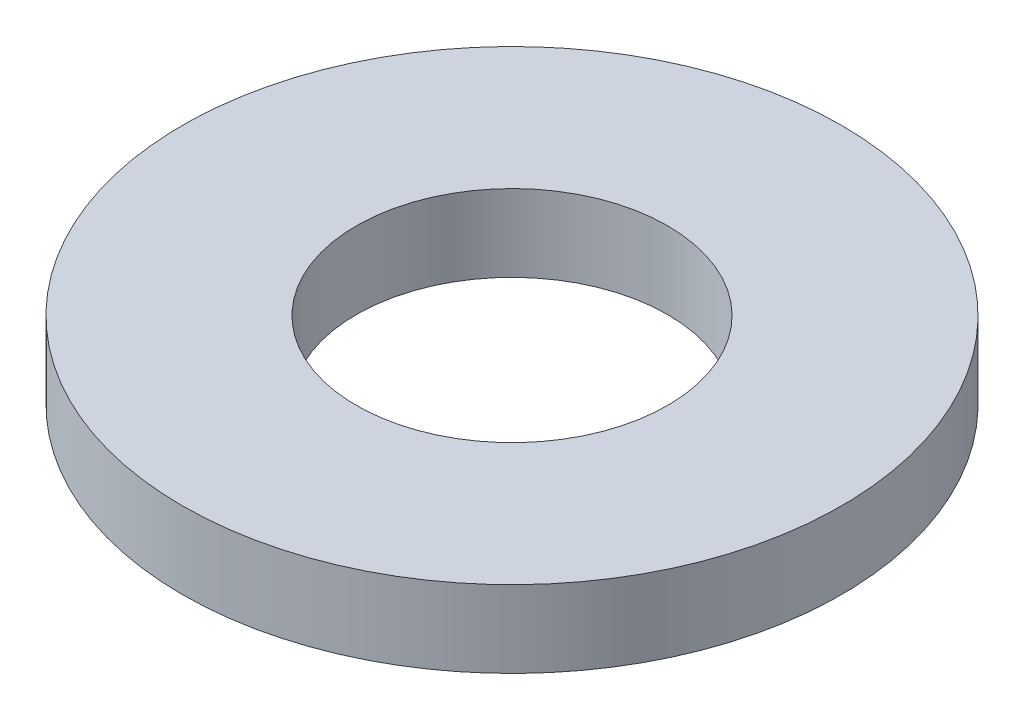
SolidWorks part; units mm, degrees
ref_plane "Front Plane" through (0, 0, 0) normal (0, 0, 1) x (1, 0, 0)
ref_plane "Top Plane" through (0, 0, 0) normal (0, 1, 0) x (1, 0, 0)
ref_plane "Right Plane" through (0, 0, 0) normal (1, 0, 0) x (0, 0, -1)
sketch "Sketch1" plane through (0, 0, 0) normal (0, 1, 0) x (1, 0, 0)
  circle A0 centre (0, 0) radius 90
  dimension "FLANGE_OD" = 180
extrude "Boss-Extrude1" add sketch "Sketch1" along normal blind 21
sketch "Sketch2" plane through (0, 0, 0) normal (0, 1, 0) x (1, 0, 0)
  circle A0 centre (0, 0) radius 42.5
  dimension "BORE_D" = 85
extrude "Cut-Extrude1" cut sketch "Sketch2" along normal through all
sketch "Sketch3" plane through (0, 21, 0) normal (0, 1, 0) x (1, 0, 0)
  circle A0 centre (0, 0) radius 26.7299 construction
  circle A1 centre (-26.7299, 0) radius 4.2347
  dimension "BOLT_D" = 8.4694
  dimension "BOLT_PCD" = 53.4599
extrude "Cut-Extrude2" cut sketch "Sketch3" against normal blind 14.2023 rebuild error yes
pattern_circular "CirPattern1" count 4 over 360 rebuild error yes
